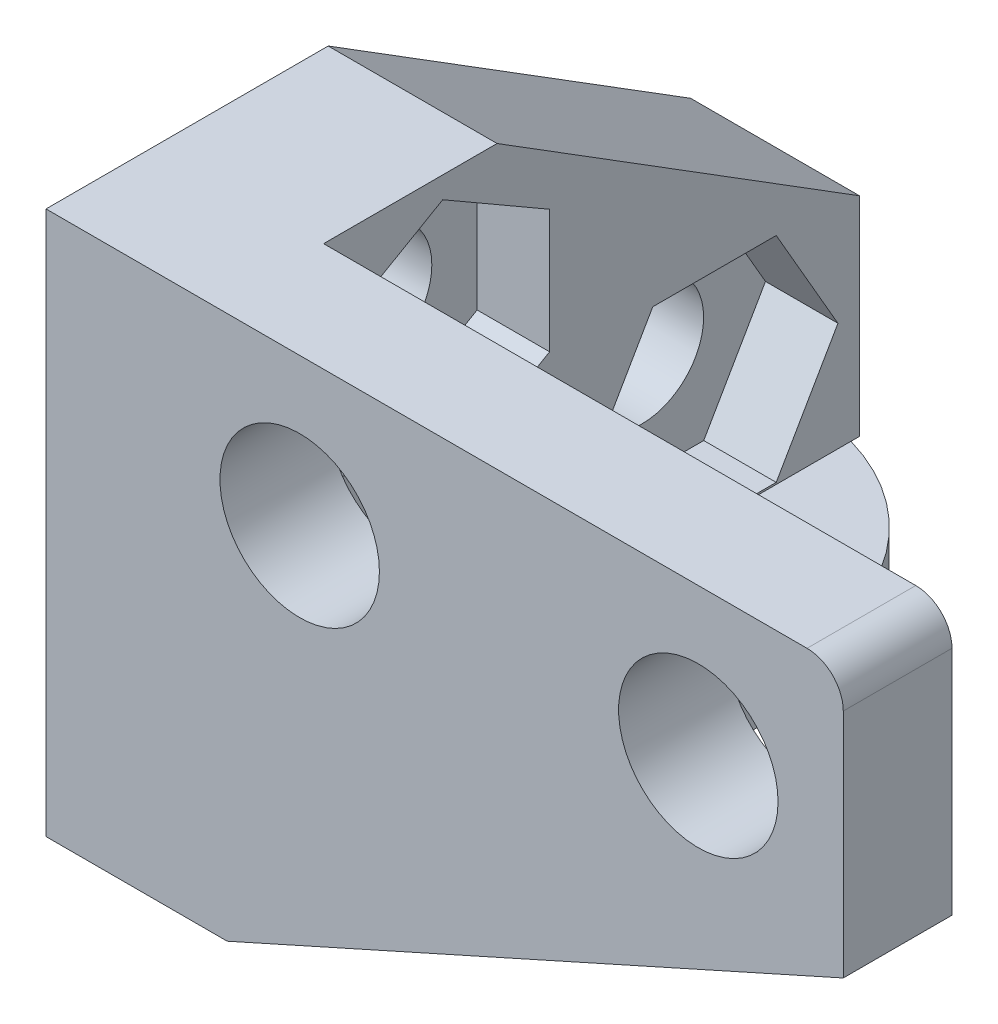
SolidWorks part; units mm, degrees
ref_plane "Спереди" through (0, 0, 0) normal (0, 0, 1) x (1, 0, 0)
ref_plane "Сверху" through (0, 0, 0) normal (0, 1, 0) x (1, 0, 0)
ref_plane "Справа" through (0, 0, 0) normal (1, 0, 0) x (0, 0, -1)
sketch "Эскиз1" plane through (0, 0, 0) normal (0, 0, 1) x (1, 0, 0)
  line L1 (-20, 25) -> (20, 25)
  line L2 (-20, 25) -> (-20, -25)
  line L3 (-20, -25) -> (20, -25)
  line L4 (20, 25) -> (20, -25)
  line L5 (-20, 25) -> (20, -25) construction
  line L6 (-20, -25) -> (20, 25) construction
  point P0 (0, 0)
  dimension "D1" = 50
  dimension "D2" = 40
extrude "Бобышка-Вытянуть1" add sketch "Эскиз1" along normal blind 5
sketch "Эскиз5" plane through (0, 0, 5) normal (0, 0, 1) x (1, 0, 0)
  line L0 (-20, 25) -> (-12.6319, 25)
  line L1 (-12.6319, 25) -> (-12.6319, 16.8645)
  line L2 (-12.6319, 16.8645) -> (13.9785, 16.8645)
  line L3 (13.9785, 16.8645) -> (14, 11)
  line L4 (14, 11) -> (-15, -2)
  line L5 (-15, -2) -> (-20, -2)
  line L6 (-20, -2) -> (-20, 25)
  line L7 (-12.6319, 25) -> (20, 25)
  line L8 (20, 25) -> (20, -25)
  line L9 (20, -25) -> (-20, -25)
  line L10 (-20, -25) -> (-20, -2)
  line M1 (20, -25) -> (20, 25)
  line M2 (20, 25) -> (-20, 25)
  line M3 (-20, 25) -> (-20, -25)
  line M4 (-20, -25) -> (20, -25)
extrude "Вырез-Вытянуть2" cut sketch "Эскиз5" against normal through all contours L4 L5 L1 L2 L3 M3 M4 M1 M2 region at (2.5012, -3.7526, 5)
fillet "Скругление2" radius 3 1 edges at (-12.6319, 16.8645, 2.5)
sketch "Эскиз6" plane through (0, 0, 5) normal (0, 0, 1) x (1, 0, 0)
  line L0 (-20, 25) -> (-17, 25)
  line L1 (-12.6319, 25) -> (-20, 25) construction
  line L2 (-17, 25) -> (-17, -2)
  line L3 (-15, -2) -> (-20, -2) construction
  line L4 (-17, -2) -> (-20, -2)
  line L5 (-20, -2) -> (-20, 25)
  line L6 (-17, -2) -> (-15, -2)
  line L7 (-15, -2) -> (-15, 1)
  line L8 (-15, 1) -> (-17, 1)
  line M4 (-12.6319, 25) -> (-20, 25)
  line M5 (-20, 25) -> (-20, -2)
  line M6 (-20, -2) -> (-15, -2)
  dimension "D1" = 3
  dimension "D2" = 3
extrude "Бобышка-Вытянуть2" add sketch "Эскиз6" along normal blind 10 contours L2 M4 M5 M6 | L7 L8 L2 M6 region at (-18.5, 11.5, 5) region at (-16, -0.5, 5)
sketch "Эскиз8" plane through (0, 0, 5) normal (0, 0, 1) x (1, 0, 0)
  line L0 (13.9785, 16.8645) -> (2.9785, 16.8645)
  line L1 (-9.6319, 16.8645) -> (13.9785, 16.8645) construction
  line L2 (2.9785, 16.8645) -> (2.9785, 6.0593)
  line L3 (14, 11) -> (-15, -2) construction
  line L4 (2.9785, 6.0593) -> (14, 11)
  line L5 (14, 11) -> (13.9785, 16.8645)
  dimension "D1" = 11
extrude "Вырез-Вытянуть3" cut sketch "Эскиз8" against normal through all
sketch "Эскиз9" plane through (0, 0, 5) normal (0, 0, 1) x (1, 0, 0)
  line L0 (-9.6319, 16.8645) -> (-20, 16.8645)
  line L1 (-20, 25) -> (-20, -2) construction
  line L2 (-20, 16.8645) -> (-20, 25)
  line L3 (-20, 25) -> (-9.6319, 25)
  line L4 (-9.6319, 25) -> (-9.6319, 16.8645)
extrude "Вырез-Вытянуть4" cut sketch "Эскиз9" against normal through all
sketch "Эскиз10" plane through (0, 0, 5) normal (0, 0, -1) x (-1, 0, 0)
  line L0 (17, 16.8645) -> (17, 25)
  line L1 (17, 25) -> (20, 25)
  line L2 (20, 25) -> (20, 16.8645)
  line L3 (20, 16.8645) -> (17, 16.8645)
  line L4 (17, 16.8645) -> (16.9146, 16.7365)
  line M1 (17, 16.8645) -> (20, 16.8645)
  line M2 (20, 16.8645) -> (20, 25)
  line M3 (20, 25) -> (17, 25)
  line M4 (17, 25) -> (17, 16.8645)
extrude "Вырез-Вытянуть5" cut sketch "Эскиз10" against normal through all contours M4 M1 M2 M3 region at (-18.5, 20.9323, 5)
fillet "Скругление3" radius 4 1 edges at (2.9785, 16.8645, 2.5)
fillet "Скругление4" radius 4 1 edges at (-15, -0.5, 5)
fillet "Скругление5" radius 4 1 edges at (-15, -0.5, 15)
sketch "Эскиз11" plane through (0, 0, 5) normal (0, 0, 1) x (1, 0, 0)
  line L0 (-17, 8.9323) -> (-21.0837, 8.9323) construction
  line L3 (-17, 16.8645) -> (-17, 1) construction
  line L4 (-21.0837, 8.9323) -> (5.5984, 8.9323) construction
  line L5 (-20, 8.9323) -> (-13, 8.9323)
  line L6 (-13, 8.9323) -> (-2, 8.9323)
  line L7 (-2, 8.9323) -> (2.879, 8.9323)
  circle A0 centre (-13, 8.9323) radius 2
  circle A1 centre (-2, 8.9323) radius 2
  dimension "D1" = 4
  dimension "D2" = 7
  dimension "D3" = 11
sketch "Эскиз12" plane through (-17, 0, 0) normal (1, 0, 0) x (0, 0, -1)
  line L0 (-9.7321, 16.8645) -> (-9.7321, 5.3907)
  line L1 (-14.4641, 16.8645) -> (-5, 16.8645) construction
  line L2 (-9.7321, 5.3907) -> (-15.9014, 5.3907)
  line L3 (-15.9014, 5.3907) -> (-15.9014, 16.8645)
  line L4 (-15.9014, 16.8645) -> (-9.7321, 16.8645)
extrude "Вырез-Вытянуть6" cut sketch "Эскиз12" against normal through all
sketch "Эскиз15" plane through (-20, 0, 0) normal (-1, 0, 0) x (0, 0, 1)
  line L0 (0, -2) -> (0, 13)
  line L1 (0, 16.8645) -> (0, -2) construction
  line L2 (0, 13) -> (9.7321, 13)
  line L3 (9.7321, 5.3907) -> (9.7321, 16.8645) construction
  line L4 (9.7321, 13) -> (9.7321, 16.8645)
  line L5 (9.7321, 16.8645) -> (0, 16.8645)
  line L6 (0, 16.8645) -> (0, 13)
  line M5 (9.7321, 5.3907) -> (9.7321, 16.8645)
  line M6 (9.7321, 16.8645) -> (0, 16.8645)
  line M7 (0, 16.8645) -> (0, -2)
  dimension "D1" = 15
extrude "Вырез-Вытянуть8" cut sketch "Эскиз15" against normal through all contours L2 M7 M5 M6 region at (-20, 14.9323, 4.866)
fillet "Скругление6" radius 8 1 edges at (-18.5, 5.3907, 9.7321)
fillet "Скругление7" radius 1 1 edges at (-18.5, 13, 9.7321)
sketch "Эскиз16" plane through (0, 0, 0) normal (0, 0, -1) x (-1, 0, 0)
  line L0 (20, 13) -> (-2, 13)
  line L1 (-2.9762, 13) -> (20, 13) construction
  line L2 (-2, 13) -> (-2, 2.1922)
  line L5 (0, 4.7241) -> (15, -2)
  line L7 (-2, 2.1922) -> (-7.7664, 2.1922)
  line L8 (-7.7664, 2.1922) -> (-7.7664, 13)
  line L9 (-7.7664, 13) -> (-2, 13)
  line M3 (20, 13) -> (-2.9762, 13)
  arc M4 (-2.9762, 13) -> (-2.9785, 12.8645) centre (1.0215, 12.8645) ccw
  line M5 (-2.9785, 12.8645) -> (-2.9785, 6.0593)
  line M6 (-2.9785, 6.0593) -> (15, -2)
  dimension "D1" = 22
extrude "Вырез-Вытянуть12" cut sketch "Эскиз16" against normal blind 10 contours L9 L8 L7 L2 M6 M5 M4 | L2 M3 M4 M5 M6 region at (2.4843, 9.4188, 0) region at (5.187, 7.3652, 0)
fillet "Скругление8" radius 1 1 edges at (2, 13, 2.5)
extrude "Вырез-Вытянуть13" cut sketch "Эскиз11" against normal blind 10 contours L5 A0 L6 | L6 A0 L5 | L6 A1 L7 | L7 A1 L6 region at (-13, 9.7811, 5) region at (-2, 9.7811, 5) region at (-2, 8.0834, 5) region at (-13, 8.0834, 5)
sketch "Эскиз18" plane through (-17, 0, 0) normal (1, 0, 0) x (0, 0, -1)
  line L0 (-5, 13) -> (-15.7866, 13)
  line L1 (-15.7866, 13) -> (-15.7866, -2)
  line L2 (-15.7866, -2) -> (-9, -2)
  line L3 (-11, -2) -> (-9, -2) construction
  line L4 (-5, 13) -> (-5, -2)
  line L5 (0, -2) -> (-9, -2) construction
  line L6 (-5, -2) -> (-9, -2)
extrude "Бобышка-Вытянуть3" add sketch "Эскиз18" against normal blind 3
sketch "Эскиз19" plane through (-17, 0, 0) normal (1, 0, 0) x (0, 0, -1)
  line L0 (-15.7866, 13) -> (-8.2866, 13)
  line L1 (-15.7866, 13) -> (-5, 13) construction
  line L2 (-8.2866, 13) -> (-8.2866, 9)
  line L4 (-8.2866, 5.8246) -> (-5.5366, 7.4123)
  line L5 (-5.5366, 7.4123) -> (-5.5366, 10.5877)
  line L6 (-5.5366, 10.5877) -> (-8.2866, 12.1754)
  line L7 (-8.2866, 12.1754) -> (-11.0366, 10.5877)
  line L8 (-11.0366, 10.5877) -> (-11.0366, 7.4123)
  line L9 (-11.0366, 7.4123) -> (-8.2866, 5.8246)
  circle A0 centre (-8.2866, 9) radius 2.75 construction
  dimension "D1" = 7.5
  dimension "D2" = 4
  dimension "D3" = 5.5
extrude "Вырез-Вытянуть14" cut sketch "Эскиз19" against normal blind 2.2 contours L8 L9 L4 L5 L6 L7 region at (-17, 6.6912, 9.6196)
sketch "Эскиз20" plane through (0, 0, 15.7866) normal (0, 0, 1) x (1, 0, 0)
  line L0 (-20, 13) -> (-17, 13)
  line L1 (-17, 13) -> (-17, -2)
  line L2 (-17, -2) -> (-20, -2)
  line L3 (-20, -2) -> (-20, 13)
extrude "Бобышка-Вытянуть5" add sketch "Эскиз20" along normal blind 4
sketch "Эскиз21" plane through (-17, 0, 0) normal (1, 0, 0) x (0, 0, -1)
  line L0 (-19.7866, -2) -> (-19.7866, 4)
  line L1 (-19.7866, -2) -> (-19.7866, 13) construction
  line L2 (-19.7866, 4) -> (-15.7866, 4)
  line L4 (-12.6112, 4) -> (-14.1989, 6.75)
  line L5 (-14.1989, 6.75) -> (-17.3743, 6.75)
  line L6 (-17.3743, 6.75) -> (-18.962, 4)
  line L7 (-18.962, 4) -> (-17.3743, 1.25)
  line L8 (-17.3743, 1.25) -> (-14.1989, 1.25)
  line L9 (-14.1989, 1.25) -> (-12.6112, 4)
  circle A0 centre (-15.7866, 4) radius 2.75 construction
  dimension "D1" = 6
  dimension "D2" = 4
  dimension "D3" = 5.5
extrude "Вырез-Вытянуть15" cut sketch "Эскиз21" against normal blind 2.2 contours L8 L9 L4 L5 L6 L7 region at (-17, 2.667, 13.4778)
sketch "Эскиз22" plane through (-17, 0, 0) normal (1, 0, 0) x (0, 0, -1)
  line L0 (-14.1989, 6.75) -> (-17.3743, 1.25)
  line L1 (-17.3743, 1.25) -> (-14.1989, 1.25)
  line L2 (-14.1989, 1.25) -> (-17.3743, 6.75)
  line L3 (-11.0366, 10.5877) -> (-5.5366, 7.4123)
  line L4 (-5.5366, 7.4123) -> (-5.5366, 10.5877)
  line L5 (-5.5366, 10.5877) -> (-11.0366, 7.4123)
  circle A0 centre (-15.7866, 4) radius 1.5
  circle A1 centre (-8.2866, 9) radius 1.5
  dimension "D1" = 3
  dimension "D2" = 3
extrude "Вырез-Вытянуть16" cut sketch "Эскиз22" against normal through all contours L2 A0 L0 | L0 A0 L2 | L2 A0 L0 | L0 A0 L2 | L5 A1 L3 | L3 A1 L5 | L5 A1 L3 | L3 A1 L5 region at (-17, 4, 14.9596) region at (-17, 4.9549, 15.7866) region at (-17, 3.0451, 15.7866) region at (-17, 4, 16.6136) region at (-17, 9.827, 8.2866) region at (-17, 9, 9.2415) region at (-17, 9, 7.3317) region at (-17, 8.173, 8.2866)
sketch "Эскиз23" plane through (0, 1, 0) normal (0, 1, 0) x (1, 0, 0)
  line L0 (-17, -5) -> (-17, -19.7866)
  line L1 (-17, -19.7866) -> (-11, -5)
  line L2 (-17, -5) -> (1, -5) construction
  line L3 (-11, -5) -> (-17, -5) construction
  line L4 (-11, -5) -> (-11, -19.7866)
  line L5 (-11, -19.7866) -> (-17, -19.7866)
  line M1 (-17, -5) -> (-17, -14.4641)
  arc M2 (-17, -14.4641) -> (-15, -11) centre (-19, -11) ccw
  line M3 (-15, -11) -> (-15, -9)
  arc M4 (-15, -9) -> (-11, -5) centre (-11, -9) cw
  line M5 (-11, -5) -> (-17, -5)
extrude "Бобышка-Вытянуть6" add sketch "Эскиз23" against normal up to surface (3 mm away) contours L5 L4 L1 | L0 L1 M4 M3 M2 | M5 M1 M2 M3 M4 region at (-15.7239, 1, 8.6966) region at (-14.3866, 1, 10.973) region at (-13, 1, 14.8577) up to face at (-16.9337, -2, 10.615)
sketch "Эскиз24" plane through (0, 0, 5) normal (0, 0, -1) x (-1, 0, 0)
  line L0 (15, -2) -> (11, -0.2069)
  line L1 (11, -0.2069) -> (11, -2)
  line L2 (11, -2) -> (15, -2)
extrude "Вырез-Вытянуть17" cut sketch "Эскиз24" against normal through all
fillet "Скругление9" radius 6 1 edges at (-11, 0.3966, 19.7866)
fillet "Скругление10" radius 2 1 edges at (-11, 0.3966, 5)
sketch "Эскиз25" plane through (0, 0, 0) normal (0, 0, -1) x (-1, 0, 0)
  line L1 (-2.731, 13.4239) -> (20.8767, 13.4239)
  line L2 (-2.731, 13.4239) -> (-2.731, -2.4603)
  line L3 (-2.731, -2.4603) -> (20.8767, -2.4603)
  line L4 (20.8767, 13.4239) -> (20.8767, -2.4603)
extrude "Вырез-Вытянуть18" cut sketch "Эскиз25" against normal blind 2
chamfer "Фаска1" distance 10 angle 32 1 edges at (-18.5, 13, 19.7866) first distance on face at (-12, 13, 8.9289)
sketch "Эскиз28" plane through (-17, 0, 0) normal (1, 0, 0) x (0, 0, -1)
  line L0 (-3.5, 13) -> (-3.5, -2)
  line L1 (-5, 13) -> (-2, 13) construction
  line L2 (-2, -2) -> (-19.4435, -2) construction
  line L3 (2.7866, 13) -> (-9.7866, 13)
  line L4 (-14.1989, 1.25) -> (-12.6112, 4)
  line L5 (-12.6112, 4) -> (-14.1989, 6.75)
  line L6 (-14.1989, 6.75) -> (-17.3743, 6.75)
  line L7 (-17.3743, 6.75) -> (-18.962, 4)
  line L8 (-18.962, 4) -> (-17.3743, 1.25)
  line L9 (-17.3743, 1.25) -> (-14.1989, 1.25)
  line L10 (-8.2866, 5.8246) -> (-5.5366, 7.4123)
  line L11 (-5.5366, 7.4123) -> (-5.5366, 10.5877)
  line L12 (-5.5366, 10.5877) -> (-8.2866, 12.1754)
  line L13 (-8.2866, 12.1754) -> (-11.0366, 10.5877)
  line L14 (-11.0366, 10.5877) -> (-11.0366, 7.4123)
  line L15 (-11.0366, 7.4123) -> (-8.2866, 5.8246)
  line L16 (-9.7866, 13) -> (-19.7866, 6.7513)
  line L17 (-19.7866, 6.7513) -> (-19.7866, -2)
  line L18 (-19.7866, -2) -> (12.7866, -2)
  line L19 (12.7866, 6.7513) -> (12.7866, -2)
  line L20 (2.7866, 13) -> (12.7866, 6.7513)
  line L21 (4.0366, 7.4123) -> (1.2866, 5.8246)
  line L22 (4.0366, 10.5877) -> (4.0366, 7.4123)
  line L23 (1.2866, 12.1754) -> (4.0366, 10.5877)
  line L24 (-1.4634, 10.5877) -> (1.2866, 12.1754)
  line L25 (-1.4634, 7.4123) -> (-1.4634, 10.5877)
  line L26 (1.2866, 5.8246) -> (-1.4634, 7.4123)
  line L27 (10.3743, 1.25) -> (7.1989, 1.25)
  line L28 (11.962, 4) -> (10.3743, 1.25)
  line L29 (10.3743, 6.75) -> (11.962, 4)
  line L30 (7.1989, 6.75) -> (10.3743, 6.75)
  line L31 (5.6112, 4) -> (7.1989, 6.75)
  line L32 (7.1989, 1.25) -> (5.6112, 4)
  line L33 (-2, 13) -> (-2, -2)
  circle A0 centre (-15.7866, 4) radius 2.75 construction
  circle A1 centre (-8.2866, 9) radius 2.75 construction
  circle A2 centre (1.2866, 9) radius 2.75 construction
  circle A3 centre (8.7866, 4) radius 2.75 construction
extrude "Бобышка-Вытянуть8" add sketch "Эскиз28" against normal blind 3 contours L3 L33 L18 L19 L20 L21 L26 L25 L24 L23 L22 L27 L32 L31 L30 L29 L28 region at (-17, 3.8958, -4.6105)
sketch "Эскиз30" plane through (0, -2, 0) normal (0, -1, 0) x (1, 0, 0)
  line L0 (2, 3.5) -> (-20, 3.5)
  line L1 (2, 5) -> (2, 2) construction
  line L2 (-20, -12.7866) -> (-20, 19.7866) construction
  line L3 (-11, 13.7866) -> (-11, 7)
  line L4 (-17, 19.7866) -> (-20, 19.7866)
  line L5 (-20, 19.7866) -> (-20, -12.7866)
  line L6 (-9, 5) -> (2, 5)
  line L7 (2, 5) -> (2, 2)
  line L8 (-9, 2) -> (2, 2)
  line L9 (-17, -12.7866) -> (-20, -12.7866)
  line L10 (-11, -6.7866) -> (-11, 0)
  arc A0 (-17, 19.7866) -> (-11, 13.7866) centre (-17, 13.7866) cw
  arc A1 (-11, 7) -> (-9, 5) centre (-9, 7) ccw
  arc A2 (-11, 0) -> (-9, 2) centre (-9, 0) cw
  arc A3 (-17, -12.7866) -> (-11, -6.7866) centre (-17, -6.7866) ccw
  line M1 (-17, 2) -> (-15, 2)
  line M2 (-15, 2) -> (-15, 19.4435)
  line M7 (-17, -12.7866) -> (-17, 2)
extrude "Бобышка-Вытянуть9" add sketch "Эскиз30" against normal blind 3 contours A3 L10 A2 L8 L7 L0 M7 M2 M1 region at (-12.3104, -2, -2.9678)
sketch "Эскиз31" plane through (0, 0, 3.5) normal (0, 0, 1) x (1, 0, 0)
  line L0 (-15, -2) -> (2, 5.6207)
  line L1 (2, 5.6207) -> (2, -2)
  line L2 (2, -2) -> (-15, -2)
extrude "Вырез-Вытянуть19" cut sketch "Эскиз31" against normal through all
sketch "Эскиз32" plane through (-20, 0, 0) normal (-1, 0, 0) x (0, 0, 1)
  line L0 (-10.3743, 1.25) -> (-7.1989, 6.75)
  line L1 (-7.1989, 6.75) -> (-5.6112, 4)
  line L2 (-5.6112, 4) -> (-11.962, 4)
  line L3 (-4.0366, 7.4123) -> (1.4634, 10.5877)
  line L4 (1.4634, 10.5877) -> (1.4634, 7.4123)
  line L5 (1.4634, 7.4123) -> (-4.0366, 10.5877)
  circle A0 centre (-1.2866, 9) radius 1.5
  circle A1 centre (-8.7866, 4) radius 1.5
  dimension "D1" = 3
extrude "Бобышка-Вытянуть10" add sketch "Эскиз32" along normal blind 3 separate body contours L0 A1 L2 | L2 A1 L0 | L0 A1 L2 | L2 A1 L0 | L3 A0 L5 | L5 A0 L3 | L3 A0 L5 | L5 A0 L3 region at (-20, 3.5225, -9.6136) region at (-20, 3.2838, -8.3731) region at (-20, 4.7162, -9.2001) region at (-20, 4.4775, -7.9596) region at (-20, 9, -2.2415) region at (-20, 8.173, -1.2866) region at (-20, 9.827, -1.2866) region at (-20, 9, -0.3317)
sketch "Эскиз33" plane through (-20, 0, 0) normal (-1, 0, 0) x (0, 0, 1)
  line L1 (-7.1989, 1.25) -> (-5.6112, 4)
  line L2 (-5.6112, 4) -> (-7.1989, 6.75)
  line L3 (-7.1989, 6.75) -> (-10.3743, 6.75)
  line L4 (-10.3743, 6.75) -> (-11.962, 4)
  line L5 (-11.962, 4) -> (-10.3743, 1.25)
  line L6 (-10.3743, 1.25) -> (-7.1989, 1.25)
  line L7 (-1.2866, 5.8246) -> (1.4634, 7.4123)
  line L8 (1.4634, 7.4123) -> (1.4634, 10.5877)
  line L9 (1.4634, 10.5877) -> (-1.2866, 12.1754)
  line L10 (-1.2866, 12.1754) -> (-4.0366, 10.5877)
  line L11 (-4.0366, 10.5877) -> (-4.0366, 7.4123)
  line L12 (-4.0366, 7.4123) -> (-1.2866, 5.8246)
  circle A0 centre (-8.7866, 4) radius 2.75 construction
  circle A1 centre (-1.2866, 9) radius 2.75 construction
extrude "Бобышка-Вытянуть11" add sketch "Эскиз33" against normal blind 0.8
sketch "Эскиз35" plane through (-17, 0, 0) normal (1, 0, 0) x (0, 0, -1)
  line L0 (10.3743, 6.75) -> (7.1989, 1.25)
  line L1 (7.1989, 1.25) -> (7.1989, 6.75)
  line L2 (7.1989, 6.75) -> (10.3743, 1.25)
  line L3 (1.2866, 5.8246) -> (1.2866, 12.1754)
  line L4 (1.2866, 12.1754) -> (-1.4634, 10.5877)
  line L5 (-1.4634, 10.5877) -> (4.0366, 7.4123)
  circle A0 centre (8.7866, 4) radius 1.5
  circle A1 centre (1.2866, 9) radius 1.5
  dimension "D1" = 3
extrude "Вырез-Вытянуть22" cut sketch "Эскиз35" against normal through all contours L2 A0 L0 | L0 A0 L2 | L2 A0 L0 | L0 A0 L2 | L3 A1 L5 | L5 A1 L3 | L3 A1 L5 | L5 A1 L3 region at (-17, 4, -9.6136) region at (-17, 4.9549, -8.7866) region at (-17, 3.0451, -8.7866) region at (-17, 4, -7.9596) region at (-17, 8.5865, -0.5704) region at (-17, 8.173, -1.7641) region at (-17, 9.827, -0.8092) region at (-17, 9.4135, -2.0028)
sketch "Эскиз36" plane through (-17, 0, 0) normal (1, 0, 0) x (0, 0, -1)
  line L0 (-5, 13) -> (-5, -2)
  line L1 (12.4435, -2) -> (-19.4435, -2) construction
  line L2 (-5, -2) -> (-20.6809, -2)
  line L3 (-20.6809, -2) -> (-20.6809, 13)
  line L4 (-20.6809, 13) -> (-5, 13)
extrude "Вырез-Вытянуть23" cut sketch "Эскиз36" against normal through all
sketch "Эскиз37" plane through (0, 1, 0) normal (0, 1, 0) x (1, 0, 0)
  line L0 (-20, -5) -> (1, -5)
  line L1 (1, -5) -> (1, -23.5443)
  line L2 (1, -23.5443) -> (-20, -23.5443)
  line L3 (-20, -23.5443) -> (-20, -5)
extrude "Вырез-Вытянуть24" cut sketch "Эскиз37" against normal through all
sketch "Эскиз38" plane through (-20, 0, 0) normal (-1, 0, 0) x (0, 0, 1)
  line L0 (5, 13) -> (5, -2)
  line L1 (5, -2) -> (-12.7866, -2)
  line L2 (-12.7866, -2) -> (-12.7866, 6.7513)
  line L3 (-12.7866, 6.7513) -> (-2.7866, 13)
  line L4 (-2.7866, 13) -> (5, 13)
  circle A0 centre (-8.7866, 4) radius 1.5
  circle A1 centre (-1.2866, 9) radius 1.5
  dimension "D1" = 3
extrude "Бобышка-Вытянуть12" add sketch "Эскиз38" along normal blind 1
sketch "Эскиз39" plane through (-21, 0, 0) normal (-1, 0, 0) x (0, 0, 1)
  line L0 (5, -2) -> (-12.7866, -2)
  line L1 (-12.7866, -2) -> (-12.7866, 6.7513)
  line L2 (-12.7866, 6.7513) -> (-2.7866, 13)
  line L3 (-2.7866, 13) -> (5, 13)
  line L4 (5, 13) -> (5, -2)
  circle A0 centre (-8.7866, 4) radius 1.5
  circle A1 centre (-1.2866, 9) radius 1.5
  dimension "D1" = 3
extrude "Вырез-Вытянуть25" cut sketch "Эскиз39" against normal blind 1
sketch "Эскиз40" plane through (-20, 0, 0) normal (-1, 0, 0) x (0, 0, 1)
  circle A0 centre (-8.7866, 4) radius 1.7
  circle A1 centre (-1.2866, 9) radius 1.7
  dimension "D1" = 3.4
extrude "Вырез-Вытянуть26" cut sketch "Эскиз40" against normal through all
sketch "Эскиз41" plane through (0, 0, 5) normal (0, 0, 1) x (1, 0, 0)
  circle A0 centre (-13, 8.9323) radius 2.2
  circle A1 centre (-2, 8.9323) radius 2.2
  dimension "D1" = 4.4
extrude "Вырез-Вытянуть27" cut sketch "Эскиз41" against normal blind 10
sketch "Эскиз42" plane through (-17, 0, 0) normal (1, 0, 0) x (0, 0, -1)
  line L0 (-2, 1) -> (-2, 13)
  line L1 (-2, 13) -> (2.7866, 13)
  line L2 (2.7866, 13) -> (-2, 13) construction
  line L3 (2.7866, 13) -> (12.7866, 6.7513)
  line L4 (12.7866, 6.7513) -> (12.7866, 1)
  line L5 (12.7866, 1) -> (-2, 1)
  line L7 (-1.4634, 10.5877) -> (-1.4634, 7.4123)
  line L8 (-1.4634, 7.4123) -> (1.2866, 5.8246)
  line L9 (1.2866, 5.8246) -> (4.0366, 7.4123)
  line L10 (4.0366, 7.4123) -> (4.0366, 10.5877)
  line L11 (4.0366, 10.5877) -> (1.2866, 12.1754)
  line L12 (1.2866, 12.1754) -> (-1.4634, 10.5877)
  line L13 (5.6112, 4) -> (7.1989, 1.25)
  line L14 (7.1989, 1.25) -> (10.3743, 1.25)
  line L15 (10.3743, 1.25) -> (11.962, 4)
  line L16 (11.962, 4) -> (10.3743, 6.75)
  line L17 (10.3743, 6.75) -> (7.1989, 6.75)
  line L18 (7.1989, 6.75) -> (5.6112, 4)
  circle A0 centre (1.2866, 9) radius 2.75 construction
  circle A1 centre (8.7866, 4) radius 2.75 construction
extrude "Бобышка-Вытянуть13" add sketch "Эскиз42" along normal blind 1.66
sketch "Эскиз44" plane through (-19.2, 0, 0) normal (1, 0, 0) x (0, 0, -1)
  line L1 (-1.4634, 7.4123) -> (1.2866, 5.8246)
  line L2 (1.2866, 5.8246) -> (4.0366, 7.4123)
  line L3 (4.0366, 7.4123) -> (4.0366, 10.5877)
  line L4 (4.0366, 10.5877) -> (1.2866, 12.1754)
  line L5 (1.2866, 12.1754) -> (-1.4634, 10.5877)
  line L6 (-1.4634, 10.5877) -> (-1.4634, 7.4123)
  line L7 (7.1989, 1.25) -> (10.3743, 1.25)
  line L8 (10.3743, 1.25) -> (11.962, 4)
  line L9 (11.962, 4) -> (10.3743, 6.75)
  line L10 (10.3743, 6.75) -> (7.1989, 6.75)
  line L11 (7.1989, 6.75) -> (5.6112, 4)
  line L12 (5.6112, 4) -> (7.1989, 1.25)
  circle A0 centre (1.2866, 9) radius 2.75 construction
  circle A1 centre (8.7866, 4) radius 2.75 construction
  circle A2 centre (1.2866, 9) radius 1.7
  circle A3 centre (8.7866, 4) radius 1.7
extrude "Бобышка-Вытянуть15" add sketch "Эскиз44" along normal blind 2
sketch "Эскиз45" plane through (-15.34, 0, 0) normal (1, 0, 0) x (0, 0, -1)
  line L1 (-1.6634, 7.2968) -> (1.2866, 5.5936)
  line L2 (1.2866, 5.5936) -> (4.2366, 7.2968)
  line L3 (4.2366, 7.2968) -> (4.2366, 10.7032)
  line L4 (4.2366, 10.7032) -> (1.2866, 12.4064)
  line L5 (1.2866, 12.4064) -> (-1.6634, 10.7032)
  line L6 (-1.6634, 10.7032) -> (-1.6634, 7.2968)
  line L7 (5.3802, 4) -> (7.0834, 1.05)
  line L8 (7.0834, 1.05) -> (10.4898, 1.05)
  line L9 (10.4898, 1.05) -> (12.193, 4)
  line L10 (12.193, 4) -> (10.4898, 6.95)
  line L11 (10.4898, 6.95) -> (7.0834, 6.95)
  line L12 (7.0834, 6.95) -> (5.3802, 4)
  circle A0 centre (1.2866, 9) radius 2.95 construction
  circle A1 centre (8.7866, 4) radius 2.95 construction
  dimension "D1" = 5.9
  dimension "D2" = 5.9
extrude "Вырез-Вытянуть28" cut sketch "Эскиз45" against normal blind 2
